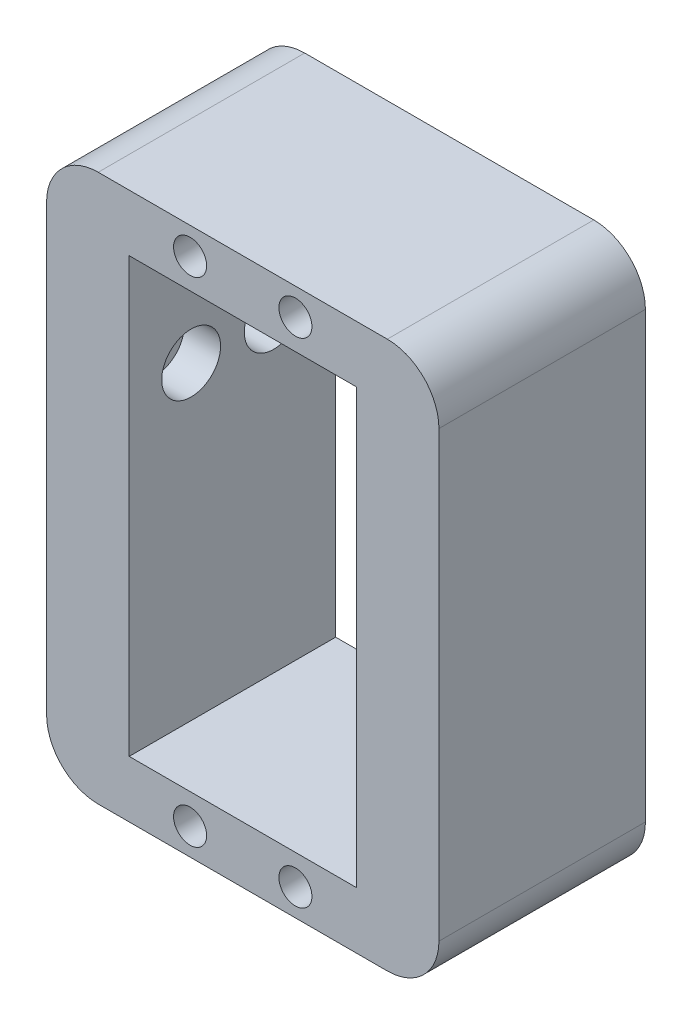
SolidWorks part; units mm, degrees
ref_plane "Front Plane" through (0, 0, 0) normal (0, 0, 1) x (1, 0, 0)
ref_plane "Top Plane" through (0, 0, 0) normal (0, 1, 0) x (1, 0, 0)
ref_plane "Right Plane" through (0, 0, 0) normal (1, 0, 0) x (0, 0, -1)
sketch "Sketch1" plane through (0, 0, 0) normal (0, 0, 1) x (1, 0, 0)
  line L1 (-11, 21) -> (11, 21)
  line L2 (-11, 21) -> (-11, -21)
  line L3 (-11, -21) -> (11, -21)
  line L4 (11, 21) -> (11, -21)
  line L5 (-11, 21) -> (11, -21) construction
  line L6 (-11, -21) -> (11, 21) construction
  line L8 (-19, 26.5) -> (19, 26.5)
  line L9 (-19, 26.5) -> (-19, -26.5)
  line L10 (-19, -26.5) -> (19, -26.5)
  line L11 (19, 26.5) -> (19, -26.5)
  line L12 (-19, 26.5) -> (19, -26.5) construction
  line L13 (-19, -26.5) -> (19, 26.5) construction
  point P0 (0, 0)
  point P6 (0, 0)
  dimension "D1" = 22
  dimension "D2" = 42
  dimension "D4" = 8
  dimension "D3" = 53
extrude "Boss-Extrude1" add sketch "Sketch1" along normal blind 20
sketch "Sketch4" plane through (0, 0, 0) normal (0, 0, -1) x (-1, 0, 0)
  circle A0 centre (-5.1, -23.9) radius 1.6
  circle A1 centre (5.1, -23.9) radius 1.6
  circle A2 centre (-5.1, 23.9) radius 1.6
  circle A3 centre (5.1, 23.9) radius 1.6
  dimension "D1" = 3.2
extrude "Cut-Extrude3" cut sketch "Sketch4" against normal through all
fillet "Fillet1" radius 5 4 edges at (-19, -26.5, 10) (19, -26.5, 10) (-19, 26.5, 10) (19, 26.5, 10)
sketch "Sketch5" plane through (-11, 0, 0) normal (1, 0, 0) x (0, 0, -1)
  line L0 (-20, 21) -> (0, 21) construction
  line L1 (-20, 21) -> (-20, -21) construction
  line L2 (0, 21) -> (0, -21) construction
  circle A0 centre (-14, 9) radius 2.85
  circle A1 centre (-14, 9) radius 1.75
  circle A2 centre (-6, 9) radius 2.85
  circle A3 centre (-6, 9) radius 1.75
  dimension "D1" = 3.5
  dimension "D2" = 5.7
  dimension "D3" = 12
  dimension "D4" = 6
  dimension "D5" = 6
extrude "Cut-Extrude4" cut sketch "Sketch5" against normal through all contours A1 | A3 region at (-11, 9, 14) region at (-11, 9, 6)
extrude "Cut-Extrude6" cut sketch "Sketch5<4>" against normal blind 3.5
sketch "Sketch5<4>" plane through (-11, 0, 0) normal (1, 0, 0) x (0, 0, -1) same geometry as "Sketch5"
